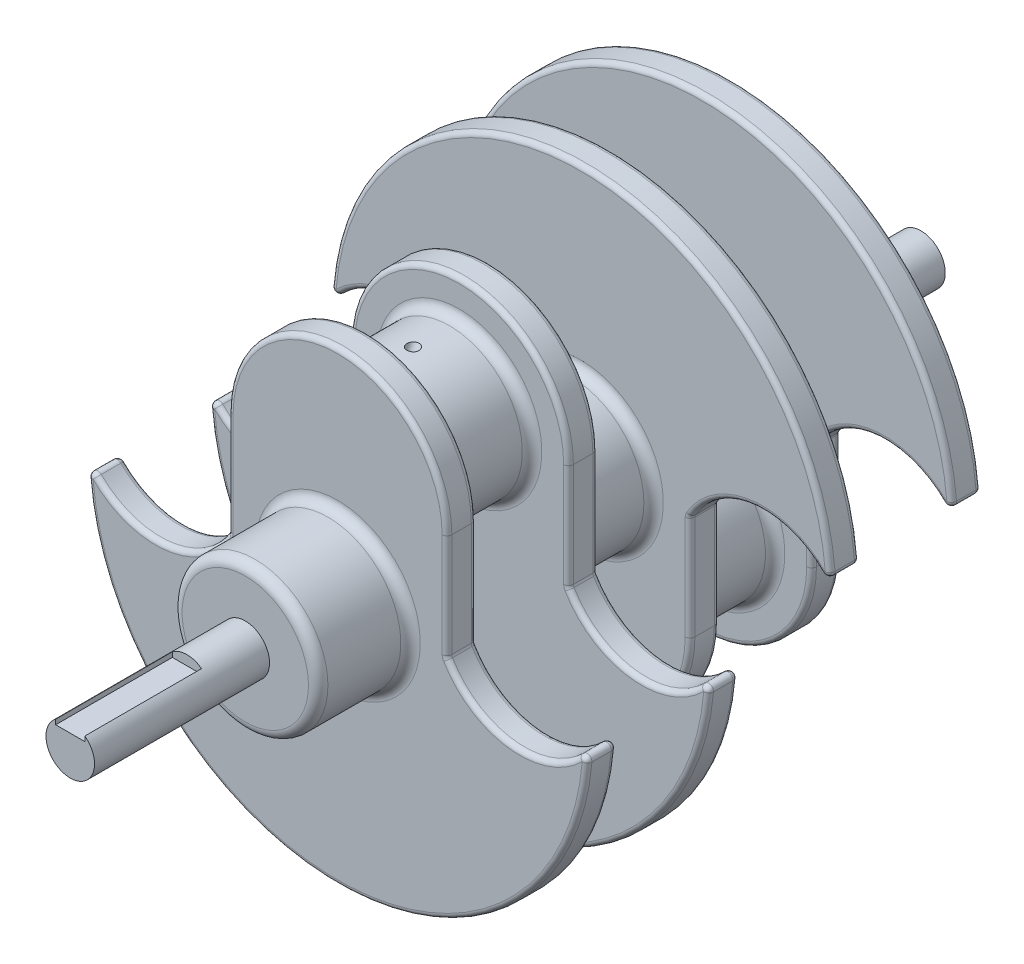
SolidWorks part; units mm, degrees
material "Low alloy steel, AISI 4340, normalized"
ref_plane "Front Plane" through (0, 0, 0) normal (0, 0, 1) x (1, 0, 0)
ref_plane "Top Plane" through (0, 0, 0) normal (0, 1, 0) x (1, 0, 0)
ref_plane "Right Plane" through (0, 0, 0) normal (1, 0, 0) x (0, 0, -1)
sketch "Sketch1" plane through (0, 0, 0) normal (0, 0, 1) x (1, 0, 0)
  circle A0 centre (0, 0) radius 30
  dimension "D1" = 30
extrude "Boss-Extrude1" add sketch "Sketch1" along normal blind 38
sketch "Sketch8" plane through (0, 0, 0) normal (0, 0, -1) x (-1, 0, 0)
  line L0 (-45, 43.2) -> (-45, 0)
  line L1 (45, 43.2) -> (45, 0)
  arc A0 (45, 43.2) -> (-45, 43.2) centre (0, 43.2) ccw
  arc A5 (-102.9647, -3) -> (102.9647, -3) centre (0, -0.3038) ccw
  arc A6 (-45, 0) -> (-102.9647, -3) centre (-74.9372, 16.949) cw
  arc A7 (45, 0) -> (102.9647, -3) centre (74.9372, 16.949) ccw
  dimension "D1" = 45
  dimension "D2" = 103
  dimension "D3" = 43.2
  dimension "D4" = 3
  dimension "D5" = 177
extrude "Boss-Extrude5" add sketch "Sketch8" along normal blind 12
sketch "Sketch2" plane through (0, 0, 38) normal (0, 0, 1) x (1, 0, 0)
  circle A0 centre (0, 0) radius 10
  dimension "D1" = 10
extrude "Boss-Extrude2" add sketch "Sketch2" along normal blind 20
sketch "Sketch9" plane through (0, 0, -12) normal (0, 0, -1) x (-1, 0, 0)
  circle A0 centre (0, 43.2) radius 30
  dimension "D2" = 30
  dimension "D1" = 43.2
extrude "Boss-Extrude6" add sketch "Sketch9" along normal blind 38
ref_plane "Plane4" through (0, 0, -100) normal (0, 0, -1) x (-1, 0, 0)
sketch "Sketch10" plane through (0, 0, -50) normal (0, 0, -1) x (-1, 0, 0)
  line L0 (-45, -43.2) -> (-45, 0)
  line L1 (45, -43.2) -> (45, 0)
  arc A0 (-45, -43.2) -> (45, -43.2) centre (0, -43.2) ccw
  arc A1 (-45, 0) -> (-102.9647, 3) centre (-74.9372, -16.949) ccw
  arc A2 (45, 0) -> (102.9647, 3) centre (74.9372, -16.949) cw
  arc A3 (-102.9647, 3) -> (102.9647, 3) centre (0, 0.3038) cw
  dimension "D1" = 45
  dimension "D4" = 3
  dimension "D5" = 177
  dimension "D3" = 103
  dimension "D2" = 43.2
extrude "Boss-Extrude7" add sketch "Sketch10" along normal blind 12 from surface starting at plane "Plane4"
ref_plane "Plane3" through (0, 0, -150) normal (0, 0, -1) x (-1, 0, 0)
sketch "Sketch12" plane through (0, 0, -150) normal (0, 0, -1) x (-1, 0, 0)
  line L2 (45, -43.2) -> (45, 0)
  line L3 (45, -43.2) -> (45, 0)
  line L4 (-45, 0) -> (-45, -43.2)
  line L5 (-45, 0) -> (-45, -43.2)
  arc A12 (-45, -43.2) -> (45, -43.2) centre (0, -43.2) ccw
  arc A13 (102.9647, 3) -> (45, 0) centre (74.9372, -16.949) ccw
  arc A14 (102.9647, 3) -> (-102.9647, 3) centre (0, 0.3038) ccw
  arc A15 (-45, 0) -> (-102.9647, 3) centre (-74.9372, -16.949) ccw
  arc A16 (-45, -43.2) -> (45, -43.2) centre (0, -43.2) ccw
  arc A17 (102.9647, 3) -> (45, 0) centre (74.9372, -16.949) ccw
  arc A18 (102.9647, 3) -> (-102.9647, 3) centre (0, 0.3038) ccw
  arc A19 (-45, 0) -> (-102.9647, 3) centre (-74.9372, -16.949) ccw
  dimension "D1" = 0
extrude "Boss-Extrude8" add sketch "Sketch12" along normal blind 12
sketch "Sketch14" plane through (0, 0, -112) normal (0, 0, -1) x (-1, 0, 0)
  circle A0 centre (0, -43.2) radius 30
  dimension "D2" = 30
  dimension "D1" = 43.2
extrude "Boss-Extrude9" add sketch "Sketch14" along normal up to next
sketch "Sketch15" plane through (0, 0, -162) normal (0, 0, -1) x (-1, 0, 0)
  circle A1 centre (0, 0) radius 30
  circle A2 centre (0, 0) radius 30
  dimension "D1" = 0
extrude "Boss-Extrude10" add sketch "Sketch15" along normal blind 38
sketch "Sketch16" plane through (0, 0, -200) normal (0, 0, -1) x (-1, 0, 0)
  circle A1 centre (0, 0) radius 10
  circle A2 centre (0, 0) radius 10
  dimension "D1" = 0
extrude "Boss-Extrude11" add sketch "Sketch16" along normal blind 40
sketch "Sketch18" plane through (0, 0, -50) normal (0, 0, -1) x (-1, 0, 0)
  line L2 (-45, 43.2) -> (-45, 0)
  line L3 (-45, 43.2) -> (-45, 0)
  line L4 (45, 0) -> (45, 43.2)
  line L5 (45, 0) -> (45, 43.2)
  arc A4 (45, 43.2) -> (-45, 43.2) centre (0, 43.2) ccw
  arc A5 (-102.9647, -3) -> (-45, 0) centre (-74.9372, 16.949) ccw
  arc A6 (-102.9647, -3) -> (102.9647, -3) centre (0, -0.3038) ccw
  arc A7 (45, 0) -> (102.9647, -3) centre (74.9372, 16.949) ccw
  arc A8 (45, 43.2) -> (-45, 43.2) centre (0, 43.2) ccw
  arc A9 (-102.9647, -3) -> (-45, 0) centre (-74.9372, 16.949) ccw
  arc A10 (-102.9647, -3) -> (102.9647, -3) centre (0, -0.3038) ccw
  arc A11 (45, 0) -> (102.9647, -3) centre (74.9372, 16.949) ccw
  dimension "D1" = 0
extrude "Boss-Extrude12" add sketch "Sketch18" along normal blind 12
sketch "Sketch19" plane through (0, 0, -62) normal (0, 0, -1) x (-1, 0, 0)
  circle A1 centre (0, 0) radius 30
  circle A2 centre (0, 0) radius 30
  dimension "D1" = 0
extrude "Boss-Extrude13" add sketch "Sketch19" along normal up to next
fillet "Fillet1" radius 2 32 edges at (0, -103.3038, -50) (-73.1591, -17.4071, -50) (-45, 21.6, -50) (45, 21.6, -50) (73.1591, -17.4071, -50) (0, -103.3038, -62) (-73.1591, -17.4071, -62) (-45, 21.6, -62) (0, 88.2, -62) (45, 21.6, -62) (73.1591, -17.4071, -62) (102.9647, -3, -56) (45, 0, -56) (-45, 0, -56) (-102.9647, -3, -56) (0, 88.2, -50) (45, 21.6, 0) (73.1591, -17.4071, 0) (0, -103.3038, 0) (-73.1591, -17.4071, 0) (-45, 21.6, 0) (0, 88.2, -12) (45, 21.6, -12) (73.1591, -17.4071, -12) (0, -103.3038, -12) (-73.1591, -17.4071, -12) (-45, 21.6, -12) (-45, 0, -6) (-102.9647, -3, -6) (102.9647, -3, -6) (45, 0, -6) (0, 88.2, 0)
fillet "Fillet2" radius 2 16 edges at (0, 103.3038, -150) (73.1591, 17.4071, -150) (45, -21.6, -150) (0, -88.2, -150) (-45, -21.6, -150) (-73.1591, 17.4071, -150) (73.1591, 17.4071, -162) (45, -21.6, -162) (0, -88.2, -162) (-45, -21.6, -162) (-73.1591, 17.4071, -162) (-102.9647, 3, -156) (-45, 0, -156) (45, 0, -156) (102.9647, 3, -156) (0, 103.3038, -162)
fillet "Fillet3" radius 2 16 edges at (45, -21.6, -100) (73.1591, 17.4071, -100) (0, 103.3038, -100) (-73.1591, 17.4071, -100) (-45, -21.6, -100) (0, -88.2, -100) (45, -21.6, -112) (73.1591, 17.4071, -112) (-73.1591, 17.4071, -112) (-45, -21.6, -112) (0, -88.2, -112) (45, 0, -106) (102.9647, 3, -106) (-102.9647, 3, -106) (-45, 0, -106) (0, 103.3038, -112)
fillet "Fillet5" radius 4 2 edges at (30, 0, 38) (30, 0, 0)
fillet "Fillet6" radius 4 2 edges at (-30, 0, -162) (-30, 0, -200)
ref_plane "Plane5" through (0, 31.75, 0) normal (0, 1, 0) x (1, 0, 0)
sketch "Sketch20" plane through (0, 0, 0) normal (1, 0, 0) x (0, 0, -1)
  line L1 (112, -73.2) -> (112, -13.2)
  line L2 (112, -73.2) -> (112, -13.2)
  dimension "D1" = 0
ref_plane "Plane6" through (0, -73.2, 0) normal (0, 1, 0) x (1, 0, 0)
sketch "Sketch21" plane through (0, 31.75, 0) normal (0, 1, 0) x (1, 0, 0)
  line L2 (-30, 196) -> (30, 196) construction
  line L3 (-30, 196) -> (-30, 166) construction
  line L4 (-30, 166) -> (30, 166) construction
  line L5 (30, 196) -> (30, 166) construction
  circle A0 centre (0, 181) radius 2.5
  point P10 (0, 196)
  point P11 (30, 181)
  dimension "D1" = 5
sketch "Sketch27" plane through (0, 0, 0) normal (0, 0, 1) x (1, 0, 0)
  line L0 (0, 73.2) -> (0, -30) construction
  circle A1 centre (0, 43.2) radius 30
  circle A2 centre (0, 43.2) radius 30 construction
  circle A3 centre (0, 0) radius 30
  circle A4 centre (0, 0) radius 30 construction
  dimension "D1" = 0
  dimension "D2" = 0
ref_plane "Plane8" through (0, 73.2, 0) normal (0, -1, 0) x (-1, 0, 0)
ref_plane "Plane9" through (0, -30, 0) normal (0, -1, 0) x (-1, 0, 0)
sketch "Sketch28" plane through (0, -30, 0) normal (0, -1, 0) x (-1, 0, 0)
  line L1 (-30, -4) -> (30, -4) construction
  line L2 (-30, -4) -> (-30, -34) construction
  line L3 (-30, -34) -> (30, -34) construction
  line L4 (30, -4) -> (30, -34) construction
  line L5 (-30, -4) -> (30, -34) construction
  line L6 (-30, -34) -> (30, -4) construction
  circle A0 centre (0, -19) radius 2.5
  point P4 (0, -19)
  dimension "D1" = 5
sketch "Sketch29" plane through (0, 73.2, 0) normal (0, -1, 0) x (-1, 0, 0)
  line L1 (30, 50) -> (-30, 50) construction
  line L2 (30, 50) -> (30, 12) construction
  line L3 (30, 12) -> (-30, 12) construction
  line L4 (-30, 50) -> (-30, 12) construction
  line L5 (30, 50) -> (-30, 12) construction
  line L6 (30, 12) -> (-30, 50) construction
  circle A0 centre (0, 31) radius 2.5
  point P4 (0, 31)
sketch "Sketch31" plane through (0, 0, 0) normal (1, 0, 0) x (0, 0, -1)
  line L0 (31, 73.2) -> (-19, -30) construction
  line L1 (50, 86.2) -> (50, 43.2) construction
  line L2 (12, 43.2) -> (12, 86.2) construction
  line L3 (50, 86.2) -> (50, 43.2) construction
  line L4 (12, 43.2) -> (12, 86.2) construction
  line L5 (50, 73.2) -> (12, 73.2) construction
ref_plane "Plane10" through (0, 73.2, -31) normal (0, -0.8999, 0.436) x (-1, 0, 0)
ref_plane "Plane11" through (0, -30, 19) normal (0, -0.8999, 0.436) x (-1, 0, 0)
combine bodies "Combine1" operation type add bodies to combine 119 109 117
fillet "Fillet7" radius 4 6 edges at (-30, 43.2, -50) (-30, 43.2, -12) (-30, 0, -62) (-30, 0, -100) (-30, -43.2, -150) (-30, -43.2, -112)
sketch "Sketch39" plane through (0, -73.2, 0) normal (0, 1, 0) x (1, 0, 0)
  line L1 (30, 146) -> (-30, 146) construction
  line L2 (30, 146) -> (30, 116) construction
  line L3 (30, 116) -> (-30, 116) construction
  line L4 (-30, 146) -> (-30, 116) construction
  line L5 (30, 146) -> (-30, 116) construction
  line L6 (30, 116) -> (-30, 146) construction
  point P4 (0, 131)
sketch "Sketch40" plane through (0, 0, 0) normal (1, 0, 0) x (0, 0, -1)
  line L0 (181, 31.75) -> (131, -73.2) construction
  line L1 (196, 31.75) -> (166, 31.75) construction
  line L2 (116, -73.2) -> (146, -73.2) construction
ref_plane "Plane12" through (0, 31.75, -181) normal (0, -0.9028, 0.4301) x (-1, 0, 0)
ref_plane "Plane13" through (0, -73.2, -131) normal (0, -0.9028, 0.4301) x (-1, 0, 0)
sketch "Sketch47" plane through (0, 73.2, -31) normal (0, -0.8999, 0.436) x (-1, 0, 0)
  ellipse E0 centre (0, 0) end of major axis (2.5, 0) minor radius 2.2498 construction
  ellipse E1 centre (0, 0) end of major axis (2.5, 0) minor radius 2.2498
sketch "Sketch48" plane through (0, -30, 19) normal (0, -0.8999, 0.436) x (-1, 0, 0)
  ellipse E0 centre (0, 0) end of major axis (2.5, 0) minor radius 2.2498 construction
  ellipse E1 centre (0, 0) end of major axis (2.5, 0) minor radius 2.2498
extrude "Cut-Extrude2" cut sketch "Sketch48" against normal through all both and the other way through all
sketch "Sketch49" plane through (0, -73.2, -131) normal (0, -0.9028, 0.4301) x (-1, 0, 0)
  circle A0 centre (0, 0) radius 2.5
  dimension "D1" = 5
extrude "Cut-Extrude3" cut sketch "Sketch49" against normal through all both and the other way through all
sketch "Sketch51" plane through (0, 0, 0) normal (1, 0, 0) x (0, 0, -1)
  line L0 (31, 73.2) -> (131, -73.2) construction
ref_plane "Plane14" through (0, 73.2, -31) normal (0, -0.8257, -0.564) x (-1, 0, 0)
sketch "Sketch53" plane through (0, 0, 58) normal (0, 0, -1) x (-1, 0, 0)
  circle A1 centre (0, 0) radius 10
  circle A2 centre (0, 0) radius 10
  dimension "D1" = 0
extrude "Boss-Extrude14" add sketch "Sketch53" against normal blind 52
sketch "Sketch54" plane through (0, 0, 110) normal (0, 0, 1) x (1, 0, 0)
  line L1 (-6, 6) -> (6, 6)
  line L2 (-6, 6) -> (-6, 14)
  line L3 (-6, 14) -> (6, 14)
  line L4 (6, 6) -> (6, 14)
  line L5 (-6, 6) -> (6, 14) construction
  line L6 (-6, 14) -> (6, 6) construction
  circle A0 centre (0, 0) radius 10 construction
  circle A1 centre (0, 0) radius 10 construction
  point P0 (0, 10)
  dimension "D1" = 12
  dimension "D2" = 8
extrude "Cut-Extrude4" cut sketch "Sketch54" against normal blind 48
equation "\"CRR\"= 43.2mm'Crank Radius"
equation "\"D1@Sketch9\"=\"CRR\""
equation "\"D1@Sketch14\"=\"CRR\""
equation "\"JR\"= 30mm'Journal Radius"
equation "\"D1@Sketch1\"=\"JR\""
equation "\"D2@Sketch9\"=\"JR\""
equation "\"D2@Sketch14\"=\"JR\""
equation "\"LT\"= 12mm'Lobe Thickness"
equation "\"D1@Boss-Extrude5\"=\"LT\""
equation "\"D1@Boss-Extrude7\"=\"LT\""
equation "\"D1@Boss-Extrude8\"=\"LT\""
equation "\"D1@Boss-Extrude12\"=\"LT\""
equation "\"D3@Sketch8\"=\"CRR\""
equation "\"D2@Sketch10\"=\"CRR\""
equation "\"JL\"= 30 + 2 * ( \"JF\" )'Journal Length"
equation "\"D1@Boss-Extrude1\"=\"JL\""
equation "\"D1@Boss-Extrude6\"=\"JL\""
equation "\"D1@Boss-Extrude10\"=\"JL\""
equation "\"LHD\"= 5mm'Lubrication Hole Diameter"
equation "\"D1@Sketch29\"=\"LHD\""
equation "\"JF\"= 4mm'Internal Journal Fillets"
equation "\"D1@Fillet7\"=\"JF\""
equation "\"D1@Fillet6\"=\"JF\""
equation "\"LR\"= 45mm'Lobe radius"
equation "\"CWR\"= 103mm'Counterweight Radius"
equation "\"D1@Sketch8\"=\"LR\""
equation "\"D2@Sketch8\"=\"CWR\""
equation "\"D3@Sketch10\"=\"CWR\""
equation "\"D1@Sketch10\"=\"LR\""
equation "\"CWA\"= 3.08923rad'Counterweight Arc"
equation "\"CWS\"= 0rad'Counterweight Slope"
equation "\"CWH\"= 3mm'Counterweight Offset"
equation "\"D5@Sketch8\"=\"CWA\""
equation "\"D5@Sketch10\"=\"CWA\""
equation "\"D4@Sketch8\"=\"CWH\""
equation "\"D4@Sketch10\"=\"CWH\""
